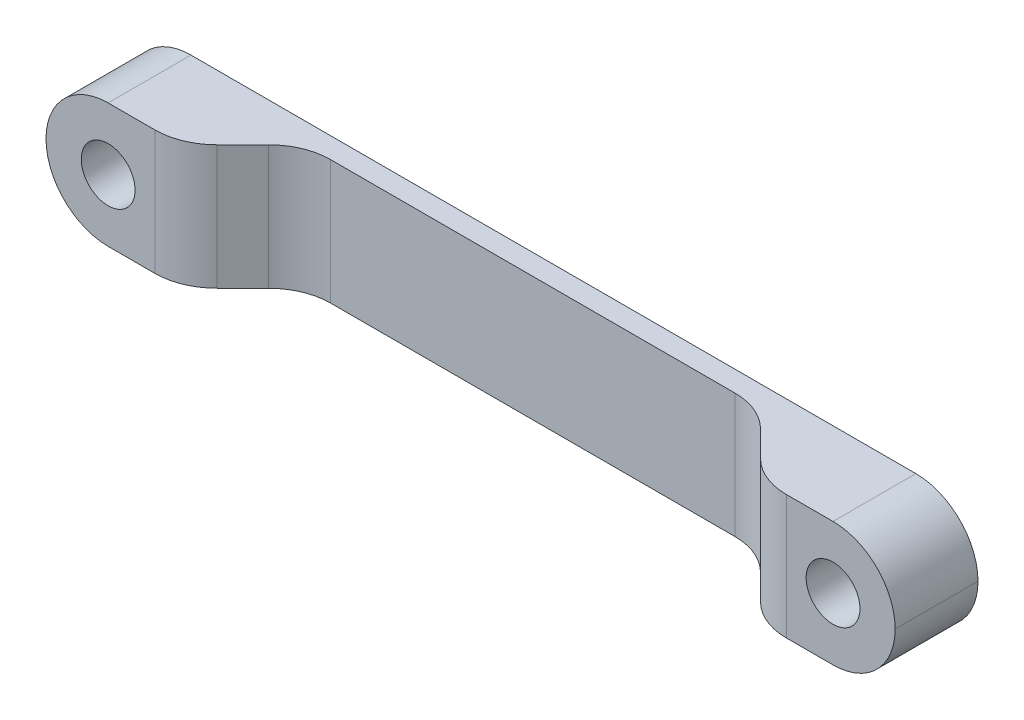
SolidWorks part; units mm, degrees
ref_plane "Front Plane" through (0, 0, 0) normal (0, 0, 1) x (1, 0, 0)
ref_plane "Top Plane" through (0, 0, 0) normal (0, 1, 0) x (1, 0, 0)
ref_plane "Right Plane" through (0, 0, 0) normal (1, 0, 0) x (0, 0, -1)
sketch "Sketch1" plane through (0, 0, 0) normal (0, 0, 1) x (1, 0, 0)
  line L0 (-20.5, 3) -> (20.5, 3)
  line L1 (20.5, 3) -> (20.5, -3)
  line L2 (20.5, -3) -> (-20.5, -3)
  line L3 (-20.5, -3) -> (-20.5, 3)
  line L4 (0, 0) -> (0, -9.7046) construction
  circle A0 centre (17.5, 0) radius 1.3
  circle A1 centre (-17.5, 0) radius 1.3
  point P4 (0, 3)
  point P5 (-20.5, 0)
  point P13 (0, 0)
  dimension "D3" = 35
  dimension "D4" = 2.6
  dimension "D1" = 3
  dimension "D2" = 3
extrude "Boss-Extrude1" add sketch "Sketch1" along normal blind 4
fillet "Fillet1" radius 3 4 edges at (-20.5, -3, 2) (-20.5, 3, 2) (20.5, -3, 2) (20.5, 3, 2)
sketch "Sketch2" plane through (0, -3, 0) normal (0, -1, 0) x (1, 0, 0)
  line L0 (-14, 4) -> (-11, 1)
  line L1 (-11, 1) -> (11, 1)
  line L2 (11, 1) -> (14, 4)
  line L3 (17.5, 0) -> (-17.5, 0) construction
  line L4 (17.5, 4) -> (-17.5, 4) construction
  point P6 (-16.2087, 5.0009)
  point P7 (15.3302, 5.0009)
  point P8 (0, 1)
  point P10 (0, 0)
  point P13 (0, 0)
  dimension "D1" = 135
  dimension "D2" = 135
  dimension "D3" = 1
  dimension "D4" = 28
extrude "Cut-Extrude1" cut sketch "Sketch2" against normal through all and the other way through all
fillet "Fillet2" radius 3 4 edges at (-14, 0, 4) (-11, 0, 1) (11, 0, 1) (14, 0, 4)
